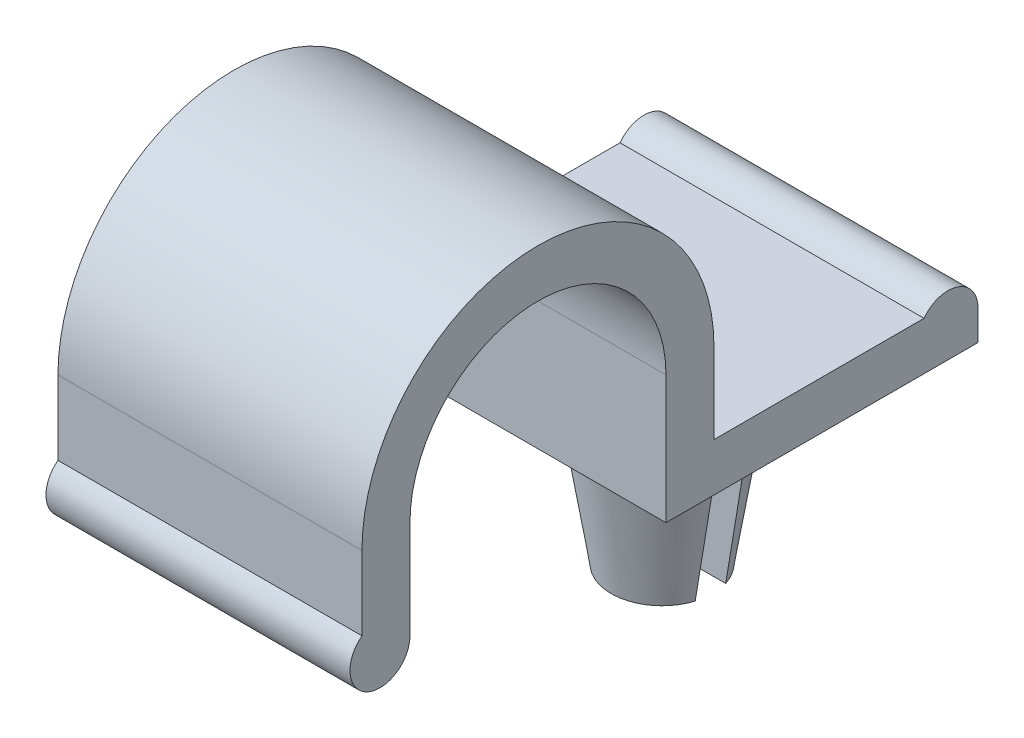
SolidWorks part; units mm, degrees
ref_plane "Front" through (0, 0, 0) normal (0, 0, 1) x (1, 0, 0)
ref_plane "Top" through (0, 0, 0) normal (0, 1, 0) x (1, 0, 0)
ref_plane "Right" through (0, 0, 0) normal (1, 0, 0) x (0, 0, -1)
other "Configuration Table"
sketch "Sketch1" plane through (0, 0, 0) normal (-1, 0, 0) x (0, 0, 1)
  line L0 (-9.65, -2) -> (-4.4, -2)
  line L1 (4.4, 0) -> (4.4, -1.85)
  line L2 (3.2, 0) -> (3.2, -2.45)
  line L3 (-3.2, 0) -> (-3.2, -3.2)
  line L4 (-4.4, 0) -> (-4.4, -2)
  line L5 (-6.9, -2) -> (-6.9, -8.7588) construction
  line L6 (-3.2, -3.2) -> (-11, -3.2)
  line L7 (-11, -3.2) -> (-11, -2.45)
  line L8 (-9.65, -2) -> (-9.65, -3.2) construction
  line L9 (3.2, 0) -> (4.4, 0) construction
  arc A0 (3.2, 0) -> (-3.2, 0) centre (0, 0) ccw
  arc A1 (4.4, 0) -> (-4.4, 0) centre (0, 0) ccw
  arc A2 (3.2, -2.45) -> (4.4, -1.85) centre (3.95, -2.45) ccw
  arc A3 (-9.65, -2) -> (-11, -2.45) centre (-10.25, -2.45) ccw
  dimension "D1" = 6.4
  dimension "D2" = 1.2
  dimension "D4" = 0.75
  dimension "D6" = 15.7
  dimension "D3" = 7.6
  dimension "D8" = 6.9
  dimension "D9" = 4.1
extrude "Base-Extrude" add sketch "Sketch1" along normal mid plane 7.6
sketch "Sketch4" plane through (0, 0, 0) normal (-1, 0, 0) x (0, 0, 1)
  line L0 (-6.9, -3.2) -> (-6.9, -7.851)
  line L2 (-6.9, -7.851) -> (-5.63, -7.851)
  line L3 (-6.9, -3.2) -> (-6.9, -2) construction
  line L4 (-5.15, -4.851) -> (-5.4, -4.851)
  line L5 (-5.4, -4.851) -> (-5.4, -3.2)
  line L6 (-5.4, -3.2) -> (-6.9, -3.2)
  line L8 (-5.15, -4.851) -> (-5.63, -7.851)
  line L9 (-11, -3.2) -> (-3.2, -3.2) construction
  dimension "D2" = 3
  dimension "D3" = 1.651
  dimension "D4" = 3
  dimension "D5" = 1.27
  dimension "D6" = 3.5
revolve "Boss-Revolve1" add sketch "Sketch4" angle 360 about L3
sketch "Sketch5" plane through (0, 0, 0) normal (-1, 0, 0) x (0, 0, 1)
  line L0 (-8.17, -7.851) -> (-5.63, -7.851) construction
  line L1 (-7.281, -7.851) -> (-6.519, -7.851)
  line L2 (-7.281, -7.851) -> (-7.281, -3.787)
  line L3 (-6.9, -2) -> (-6.9, -8.7588) construction
  line L4 (-6.519, -7.851) -> (-6.519, -3.787)
  arc A0 (-6.519, -3.787) -> (-7.281, -3.787) centre (-6.9, -3.787) ccw
  dimension "D1" = 0.762
  dimension "D3" = 4.064
extrude "Cut-Extrude1" cut sketch "Sketch5" against normal through all and the other way through all
sketch "Sketch6" plane through (-3.8, 0, 0) normal (-1, 0, 0) x (0, 0, 1)
  point P0 (0, 0)
sketch "Sketch7" plane through (3.8, 0, 0) normal (1, 0, 0) x (0, 0, -1)
  point P0 (0, 0)
ref_axis "Clip Axis" through (-3.8, 0, 0) along (1, 0, 0)
other "RPoint1"
ref_axis "Axis1" through (1.2, 0, 0) along (-1, 0, 0)
other "RPoint2"
ref_axis "Axis2" through (-1.2, 0, 0) along (1, 0, 0)
sketch "FilterSketch" plane through (0, 0, 0) normal (0, 0, 1) x (1, 0, 0)
  circle A0 centre (0, 0) radius 3.2
  circle A1 centre (0, 0) radius 3.2
  circle A2 centre (0, 0) radius 2.35
  dimension "NominalDiameter" = 6.4
  dimension "InnerDiameter" = 4.7
  dimension "OuterDiameter" = 6.4
ref_axis "Axis of Rotation" through (0, -3.2, -6.9) along (0, -1, 0)
